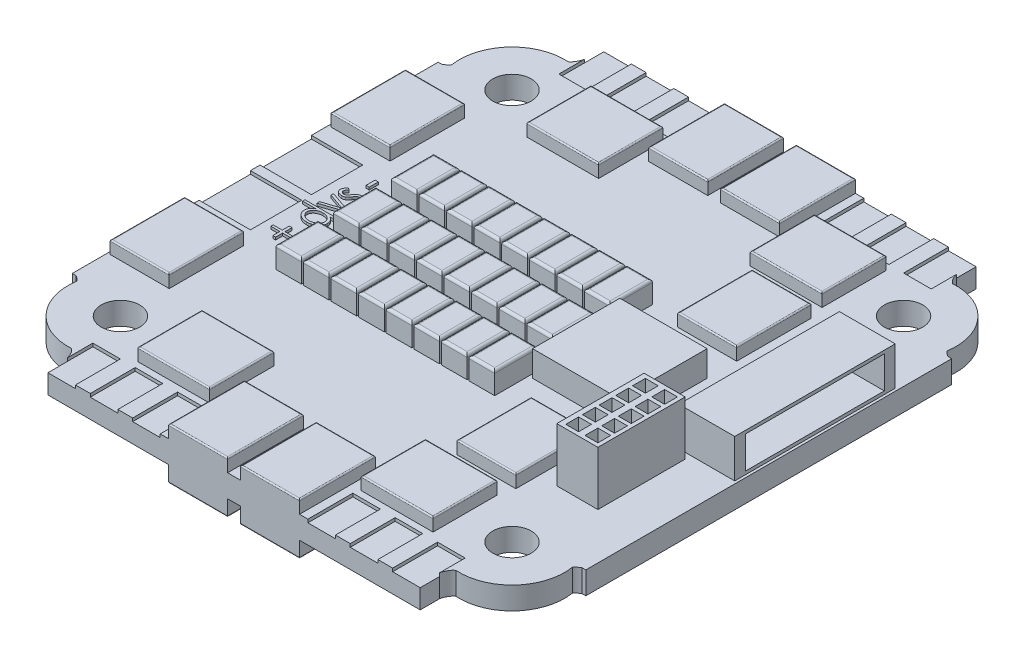
SolidWorks part; units mm, degrees
ref_plane "Ön Düzlem" through (0, 0, 0) normal (0, 0, 1) x (1, 0, 0)
ref_plane "Üst Düzlem" through (0, 0, 0) normal (0, 1, 0) x (1, 0, 0)
ref_plane "Sağ Düzlem" through (0, 0, 0) normal (1, 0, 0) x (0, 0, -1)
sketch "Çizim1" plane through (0, 0, 0) normal (0, 1, 0) x (1, 0, 0)
  line L0 (0, 44.0782) -> (0, -46.2011) construction
  line L1 (20, -21.65) -> (-20, -21.65)
  line L2 (20, -21.65) -> (20, 21.65)
  line L3 (20, 21.65) -> (-20, 21.65)
  line L4 (-20, -21.65) -> (-20, 21.65)
  line L5 (20, -21.65) -> (-20, 21.65) construction
  line L6 (20, 21.65) -> (-20, -21.65) construction
  line L7 (-44.1341, 0) -> (49.6089, 0) construction
  line L9 (15.25, -15.25) -> (-15.25, -15.25) construction
  line L10 (15.25, -15.25) -> (15.25, 15.25) construction
  line L11 (15.25, 15.25) -> (-15.25, 15.25) construction
  line L12 (-15.25, -15.25) -> (-15.25, 15.25) construction
  line L13 (15.25, -15.25) -> (-15.25, 15.25) construction
  line L14 (15.25, 15.25) -> (-15.25, -15.25) construction
  point P0 (0, 0)
  point P10 (0, 0)
  dimension "D1" = 40
  dimension "D2" = 43.3
  dimension "D3" = 30.5
  dimension "D4" = 30.5
extrude "Yükseklik-Ekstrüzyon1" add sketch "Çizim1" along normal blind 1.75
sketch "Çizim2" plane through (0, 0, 0) normal (0, 1, 0) x (1, 0, 0)
  line L1 (15.25, -15.25) -> (-15.25, -15.25) construction
  line L2 (15.25, -15.25) -> (15.25, 15.25) construction
  line L3 (15.25, 15.25) -> (-15.25, 15.25) construction
  line L4 (-15.25, -15.25) -> (-15.25, 15.25) construction
  line L5 (15.25, -15.25) -> (-15.25, 15.25) construction
  line L6 (15.25, 15.25) -> (-15.25, -15.25) construction
  circle A0 centre (-15.25, 15.25) radius 1.5
  circle A1 centre (15.25, 15.25) radius 1.5
  circle A2 centre (15.25, -15.25) radius 1.5
  circle A3 centre (-15.25, -15.25) radius 1.5
  point P0 (0, 0)
  dimension "D1" = 30.5
  dimension "D2" = 30.5
extrude "Kes-Ekstrüzyon1" cut sketch "Çizim2" along normal blind 1.75
sketch "Çizim3" plane through (0, 0, 0) normal (0, 1, 0) x (1, 0, 0)
  line L0 (-19.297, 14.593) -> (-19.4339, 14.3985) construction
  line L1 (-19.4339, 14.3985) -> (-19.7178, 14.25) construction
  line L2 (-20, 21.65) -> (-20, -21.65) construction
  line L3 (-19.7178, 14.25) -> (-20, 14.25)
  line L4 (-20, 21.65) -> (-20, 13.5542) construction
  line L5 (-20, 14.25) -> (-20, 21.65)
  line L6 (-20, 21.65) -> (-14.5, 21.65)
  line L7 (20, 21.65) -> (-20, 21.65) construction
  line L8 (-14.5, 21.65) -> (-14.5, 20.1378)
  line L9 (-14.9713, 19.3405) -> (-14.7537, 19.4813) construction
  line L10 (-14.7537, 19.4813) -> (-14.5714, 19.809) construction
  line L11 (-14.5714, 19.809) -> (-14.5, 20.1378) construction
  line L12 (20, 21.65) -> (14.5, 21.65)
  line L13 (14.5, 21.65) -> (14.5, 20.1378)
  line L14 (14.9713, 19.3405) -> (14.7537, 19.4813) construction
  line L15 (0, 29.2521) -> (0, -30.7082) construction
  line L16 (-36.8808, 0) -> (40.0068, 0) construction
  line L17 (14.7537, 19.4813) -> (14.5714, 19.809) construction
  line L18 (14.5714, 19.809) -> (14.5, 20.1378) construction
  line L19 (20, 14.25) -> (20, 21.65)
  line L20 (19.7178, 14.25) -> (20, 14.25)
  line L21 (19.297, 14.593) -> (19.4339, 14.3985) construction
  line L22 (19.4339, 14.3985) -> (19.7178, 14.25) construction
  line L23 (14.9713, -19.3405) -> (14.7537, -19.4813) construction
  line L24 (14.7537, -19.4813) -> (14.5714, -19.809) construction
  line L25 (14.5714, -19.809) -> (14.5, -20.1378) construction
  line L26 (19.297, -14.593) -> (19.4339, -14.3985) construction
  line L27 (19.4339, -14.3985) -> (19.7178, -14.25) construction
  line L28 (19.7178, -14.25) -> (20, -14.25)
  line L29 (20, -14.25) -> (20, -21.65)
  line L30 (20, -21.65) -> (14.5, -21.65)
  line L31 (14.5, 18.3234) -> (-14.5, 18.3234) construction
  line L32 (14.5, -21.65) -> (14.5, -20.1378)
  line L33 (14.5, 18.3234) -> (14.5, 24.9766) construction
  line L34 (-20, -21.65) -> (-14.5, -21.65)
  line L35 (-14.5, -21.65) -> (-14.5, -20.1378)
  line L36 (-14.9713, -19.3405) -> (-14.7537, -19.4813) construction
  line L37 (-14.7537, -19.4813) -> (-14.5714, -19.809) construction
  line L38 (-14.5714, -19.809) -> (-14.5, -20.1378) construction
  line L39 (-20, -14.25) -> (-20, -21.65)
  line L40 (-19.7178, -14.25) -> (-20, -14.25)
  line L41 (-19.297, -14.593) -> (-19.4339, -14.3985) construction
  line L42 (-19.4339, -14.3985) -> (-19.7178, -14.25) construction
  line L48 (14.5, 24.9766) -> (-14.5, 24.9766) construction
  line L49 (-14.5, 18.3234) -> (-14.5, 24.9766) construction
  line L50 (14.5, 18.3234) -> (-14.5, 24.9766) construction
  line L51 (14.5, 24.9766) -> (-14.5, 18.3234) construction
  line L52 (-14.1712, -14.25) -> (-25.8288, -14.25) construction
  line L53 (-14.1712, -14.25) -> (-14.1712, 14.25) construction
  line L54 (-14.1712, 14.25) -> (-25.8288, 14.25) construction
  line L55 (-25.8288, -14.25) -> (-25.8288, 14.25) construction
  line L56 (-14.1712, -14.25) -> (-25.8288, 14.25) construction
  line L57 (-14.1712, 14.25) -> (-25.8288, -14.25) construction
  arc A0 (14.9713, 19.3405) -> (19.297, 14.593) centre (15.25, 15.25) cw
  circle A1 centre (0, 0) radius 6.746 construction
  arc A2 (14.9713, -19.3405) -> (19.297, -14.593) centre (15.25, -15.25) ccw
  arc A3 (-14.9713, -19.3405) -> (-19.297, -14.593) centre (-15.25, -15.25) cw
  arc A5 (-14.9713, 19.3405) -> (-19.297, 14.593) centre (-15.25, 15.25) ccw
  spline S0 degree 2 poles (-19.297, 14.593) (-19.4339, 14.3985) (-19.7178, 14.25) knots 0 0 0 1 1 1
  spline S1 degree 3 poles (-14.9713, 19.3405) (-14.7537, 19.4813) (-14.5714, 19.809) (-14.5, 20.1378) knots 0 0 0 0 1 1 1 1
  spline S2 degree 3 poles (14.9713, 19.3405) (14.7537, 19.4813) (14.5714, 19.809) (14.5, 20.1378) knots 0 0 0 0 1 1 1 1
  spline S3 degree 2 poles (19.297, 14.593) (19.4339, 14.3985) (19.7178, 14.25) knots 0 0 0 1 1 1
  spline S4 degree 3 poles (14.9713, -19.3405) (14.7537, -19.4813) (14.5714, -19.809) (14.5, -20.1378) knots 0 0 0 0 1 1 1 1
  spline S5 degree 2 poles (19.297, -14.593) (19.4339, -14.3985) (19.7178, -14.25) knots 0 0 0 1 1 1
  spline S6 degree 3 poles (-14.9713, -19.3405) (-14.7537, -19.4813) (-14.5714, -19.809) (-14.5, -20.1378) knots 0 0 0 0 1 1 1 1
  spline S7 degree 2 poles (-19.297, -14.593) (-19.4339, -14.3985) (-19.7178, -14.25) knots 0 0 0 1 1 1
  point P43 (0, 21.65)
  point P61 (-20, 0)
  dimension "D1" = 29
  dimension "D2" = 28.5
extrude "Kes-Ekstrüzyon4" cut sketch "Çizim3" along normal blind 1.75
sketch "Çizim5" plane through (0, 0, 0) normal (0, 1, 0) x (1, 0, 0)
  line L0 (0, 30.9186) -> (0, -32.6939) construction
  line L1 (-49.0396, 0) -> (40.1136, 0) construction
  line L2 (-10.125, 21.65) -> (-10.125, 17.2464) construction
  line L3 (-14.5, 21.65) -> (-5.75, 21.65) construction
  line L4 (-14.5, 21.65) -> (-14.5, 18.15) construction
  line L5 (-14.5, 18.15) -> (-5.75, 18.15) construction
  line L6 (-5.75, 21.65) -> (-5.75, 18.15) construction
  line L7 (-14.5, 21.65) -> (-12.3523, 21.65)
  line L8 (-14.5, 21.65) -> (-14.5, 18.15)
  line L9 (-14.5, 18.15) -> (-12.3523, 18.15)
  line L10 (-12.3523, 21.65) -> (-12.3523, 18.15)
  line L11 (-5.75, 18.15) -> (-7.8977, 18.15)
  line L12 (-5.75, 21.65) -> (-5.75, 18.15)
  line L13 (-5.75, 21.65) -> (-7.8977, 21.65)
  line L14 (-7.8977, 21.65) -> (-7.8977, 18.15)
  line L15 (-5.75, 19.9) -> (-14.5, 19.9) construction
  line L16 (9.05, 21.65) -> (11.2, 18.15) construction
  line L17 (-9.05, 18.15) -> (-11.2, 18.15)
  line L18 (-9.05, 18.15) -> (-9.05, 21.65)
  line L19 (-9.05, 21.65) -> (-11.2, 21.65)
  line L20 (-11.2, 18.15) -> (-11.2, 21.65)
  line L21 (-9.05, 18.15) -> (-11.2, 21.65) construction
  line L22 (-9.05, 21.65) -> (-11.2, 18.15) construction
  line L23 (9.05, 18.15) -> (11.2, 21.65) construction
  line L24 (5.75, 19.9) -> (14.5, 19.9) construction
  line L25 (5.75, 21.65) -> (5.75, 18.15) construction
  line L26 (14.5, 18.15) -> (5.75, 18.15) construction
  line L27 (14.5, 21.65) -> (14.5, 18.15) construction
  line L28 (14.5, 21.65) -> (5.75, 21.65) construction
  line L29 (10.125, 21.65) -> (10.125, 17.2464) construction
  line L30 (11.2, 18.15) -> (11.2, 21.65)
  line L31 (9.05, 21.65) -> (11.2, 21.65)
  line L32 (9.05, 18.15) -> (9.05, 21.65)
  line L33 (9.05, 18.15) -> (11.2, 18.15)
  line L34 (7.8977, 21.65) -> (7.8977, 18.15)
  line L35 (5.75, 21.65) -> (7.8977, 21.65)
  line L36 (5.75, 21.65) -> (5.75, 18.15)
  line L37 (5.75, 18.15) -> (7.8977, 18.15)
  line L38 (12.3523, 21.65) -> (12.3523, 18.15)
  line L39 (14.5, 18.15) -> (12.3523, 18.15)
  line L40 (14.5, 21.65) -> (14.5, 18.15)
  line L41 (14.5, 21.65) -> (12.3523, 21.65)
  line L42 (10.125, -21.65) -> (10.125, -17.2464) construction
  line L43 (14.5, -21.65) -> (5.75, -21.65) construction
  line L44 (14.5, -21.65) -> (14.5, -18.15) construction
  line L45 (14.5, -18.15) -> (5.75, -18.15) construction
  line L46 (5.75, -21.65) -> (5.75, -18.15) construction
  line L47 (5.75, -19.9) -> (14.5, -19.9) construction
  line L48 (9.05, -18.15) -> (11.2, -21.65) construction
  line L49 (-9.05, -21.65) -> (-11.2, -18.15) construction
  line L50 (-9.05, -18.15) -> (-11.2, -21.65) construction
  line L51 (9.05, -21.65) -> (11.2, -18.15) construction
  line L52 (-5.75, -19.9) -> (-14.5, -19.9) construction
  line L53 (-5.75, -21.65) -> (-5.75, -18.15) construction
  line L54 (-14.5, -18.15) -> (-5.75, -18.15) construction
  line L55 (-14.5, -21.65) -> (-14.5, -18.15) construction
  line L56 (-14.5, -21.65) -> (-5.75, -21.65) construction
  line L57 (-10.125, -21.65) -> (-10.125, -17.2464) construction
  line L58 (14.5, -21.65) -> (12.3523, -21.65)
  line L59 (14.5, -21.65) -> (14.5, -18.15)
  line L60 (14.5, -18.15) -> (12.3523, -18.15)
  line L61 (12.3523, -21.65) -> (12.3523, -18.15)
  line L62 (5.75, -18.15) -> (7.8977, -18.15)
  line L63 (5.75, -21.65) -> (5.75, -18.15)
  line L64 (5.75, -21.65) -> (7.8977, -21.65)
  line L65 (7.8977, -21.65) -> (7.8977, -18.15)
  line L66 (9.05, -18.15) -> (11.2, -18.15)
  line L67 (9.05, -18.15) -> (9.05, -21.65)
  line L68 (9.05, -21.65) -> (11.2, -21.65)
  line L69 (11.2, -18.15) -> (11.2, -21.65)
  line L70 (-11.2, -18.15) -> (-11.2, -21.65)
  line L71 (-9.05, -21.65) -> (-11.2, -21.65)
  line L72 (-9.05, -18.15) -> (-9.05, -21.65)
  line L73 (-9.05, -18.15) -> (-11.2, -18.15)
  line L74 (-7.8977, -21.65) -> (-7.8977, -18.15)
  line L75 (-5.75, -21.65) -> (-7.8977, -21.65)
  line L76 (-5.75, -21.65) -> (-5.75, -18.15)
  line L77 (-5.75, -18.15) -> (-7.8977, -18.15)
  line L78 (-12.3523, -21.65) -> (-12.3523, -18.15)
  line L79 (-14.5, -18.15) -> (-12.3523, -18.15)
  line L80 (-14.5, -21.65) -> (-14.5, -18.15)
  line L81 (-14.5, -21.65) -> (-12.3523, -21.65)
  point P18 (-10.125, 19.9)
  point P39 (10.125, 19.9)
  point P72 (10.125, -19.9)
  point P73 (-10.125, -19.9)
  dimension "D1" = 8.75
  dimension "D2" = 3.5
  dimension "D3" = 2.15
extrude "Kes-Ekstrüzyon5" cut sketch "Çizim5" along normal blind 1 from offset 1.5
sketch "Çizim6" plane through (0, 0, 0) normal (0, 1, 0) x (1, 0, 0)
  line L0 (-37.3382, 0) -> (45.0839, 0) construction
  line L1 (-20, 14.25) -> (-20, -14.25) construction
  line L2 (-15.9, -4.375) -> (-20, -4.375) construction
  line L3 (-15.9, -4.375) -> (-15.9, 4.375) construction
  line L4 (-15.9, 4.375) -> (-20, 4.375) construction
  line L5 (-20, -4.375) -> (-20, 4.375) construction
  line L6 (-15.9, -4.375) -> (-20, 4.375) construction
  line L7 (-15.9, 4.375) -> (-20, -4.375) construction
  line L8 (-20, -4.375) -> (-20, -0.375)
  line L9 (-20, 4.375) -> (-16, 4.375)
  line L10 (-20, 4.375) -> (-20, 0.375)
  line L11 (-20, 0.375) -> (-16, 0.375)
  line L12 (-16, 4.375) -> (-16, 0.375)
  line L13 (-20, -4.375) -> (-16, -4.375)
  line L14 (-16, -4.375) -> (-16, -0.375)
  line L15 (-20, -0.375) -> (-16, -0.375)
  point P3 (-17.95, 0)
  dimension "D1" = 8.75
  dimension "D2" = 4.1
  dimension "D3" = 4
  dimension "D4" = 4
extrude "Kes-Ekstrüzyon7" cut sketch "Çizim6" along normal blind 1 from offset 1.5
sketch "Çizim7" plane through (0, 0, 0) normal (0, 1, 0) x (1, 0, 0)
  line L0 (12, 0) -> (-20, 0) construction
  line L1 (-20, 14.25) -> (-20, 4.375) construction
  line L2 (-15.2, -11.5) -> (-20, -11.5) construction
  line L3 (-15.2, -11.5) -> (-15.2, 11.5) construction
  line L4 (-15.2, 11.5) -> (-20, 11.5) construction
  line L5 (-20, -11.5) -> (-20, 11.5) construction
  line L6 (-15.2, -11.5) -> (-20, 11.5) construction
  line L7 (-15.2, 11.5) -> (-20, -11.5) construction
  line L8 (-19.8, 11.9264) -> (-19.8, -13.8708) construction
  line L9 (-19.8, -11.5) -> (-15.2, -11.5)
  line L10 (-19.8, 11.5) -> (-15.2, 11.5)
  line L11 (-19.8, 11.5) -> (-19.8, 5.7)
  line L12 (-19.8, 5.7) -> (-15.2, 5.7)
  line L13 (-15.2, 11.5) -> (-15.2, 5.7)
  line L14 (-15.2, -11.5) -> (-15.2, -5.7)
  line L15 (-19.8, -11.5) -> (-19.8, -5.7)
  line L16 (-19.8, -5.7) -> (-15.2, -5.7)
  line L17 (12, 23.8694) -> (12, -27.9826) construction
  line L18 (20, -14.25) -> (20, 14.25) construction
  line L19 (-20, 21.0492) -> (-20, -26.7007) construction
  line L20 (-4, 16.02) -> (-4, -18.6893) construction
  line L21 (11.8, -11.5) -> (11.8, -5.7)
  line L22 (11.8, -11.5) -> (7.2, -11.5)
  line L23 (7.2, -11.5) -> (7.2, -5.7)
  line L24 (11.8, -5.7) -> (7.2, -5.7)
  line L25 (11.8, 11.5) -> (11.8, 5.7)
  line L26 (11.8, 5.7) -> (7.2, 5.7)
  line L27 (7.2, 11.5) -> (7.2, 5.7)
  line L28 (11.8, 11.5) -> (7.2, 11.5)
  point P3 (-17.6, 0)
  point P16 (-17.5, -11.5)
  point P19 (-17.5, -5.7)
  dimension "D1" = 23
  dimension "D2" = 0.2
  dimension "D3" = 5.8
  dimension "D4" = 8
extrude "Yükseklik-Ekstrüzyon2" add sketch "Çizim7" along normal blind 2.75 and the other way blind 1.25
sketch "Çizim9" plane through (0, 0, 0) normal (0, 1, 0) x (1, 0, 0)
  line L0 (11.8, 15.4181) -> (11.8, -15.0147) construction
  line L1 (-13.0732, 0) -> (28.7719, 0) construction
  line L2 (-13.0732, 3.4) -> (30.1552, 3.4) construction
  line L4 (11.8, 3.4) -> (5, 3.4)
  line L5 (11.8, 3.4) -> (11.8, -3.4)
  line L6 (11.8, -3.4) -> (5, -3.4)
  line L7 (5, 3.4) -> (5, -3.4)
  dimension "D1" = 3.4
  dimension "D2" = 6.8
  dimension "D3" = 6.8
extrude "Yükseklik-Ekstrüzyon3" add sketch "Çizim9" along normal blind 3.75
sketch "Çizim10" plane through (0, 0, 0) normal (0, 1, 0) x (1, 0, 0)
  line L0 (0, 23.2569) -> (0, -24.4096) construction
  line L1 (5.75, 21.65) -> (-5.75, 21.65) construction
  line L2 (5.1, 15.75) -> (-5.1, 15.75) construction
  line L3 (5.1, 15.75) -> (5.1, 21.65) construction
  line L4 (5.1, 21.65) -> (-5.1, 21.65) construction
  line L5 (-5.1, 15.75) -> (-5.1, 21.65) construction
  line L6 (5.1, 15.75) -> (-5.1, 21.65) construction
  line L7 (5.1, 21.65) -> (-5.1, 15.75) construction
  line L8 (-5.1, 15.75) -> (-0.5021, 15.75)
  line L9 (5.1, 21.65) -> (0.5021, 21.65)
  line L10 (5.1, 21.65) -> (5.1, 15.75)
  line L11 (5.1, 15.75) -> (0.5021, 15.75)
  line L12 (0.5021, 21.65) -> (0.5021, 15.75)
  line L13 (-0.5021, 21.65) -> (-0.5021, 15.75)
  line L14 (-5.1, 21.65) -> (-0.5021, 21.65)
  line L15 (-5.1, 21.65) -> (-5.1, 15.75)
  line L16 (-34.7799, 0) -> (34.025, 0) construction
  line L17 (-17.6922, 17.65) -> (20.1896, 17.65) construction
  line L18 (-12.3523, 18.15) -> (-14.5, 18.15) construction
  line L19 (-17.6922, 15.15) -> (18.3088, 15.15) construction
  line L20 (11.5, 17.65) -> (11.5, 12.65)
  line L21 (11.5, 12.65) -> (-11.5, 12.65) construction
  line L22 (11.5, 12.65) -> (11.5, 17.65) construction
  line L23 (11.5, 17.65) -> (-11.5, 17.65) construction
  line L24 (-11.5, 12.65) -> (-11.5, 17.65) construction
  line L25 (11.5, 12.65) -> (-11.5, 17.65) construction
  line L26 (11.5, 17.65) -> (-11.5, 12.65) construction
  line L27 (-11.5, 17.65) -> (-5.9038, 17.65)
  line L28 (-11.5, 17.65) -> (-11.5, 12.65)
  line L29 (-11.5, 12.65) -> (-5.9038, 12.65)
  line L30 (-5.9038, 17.65) -> (-5.9038, 12.65)
  line L31 (11.5, 17.65) -> (5.9038, 17.65)
  line L32 (5.9038, 17.65) -> (5.9038, 12.65)
  line L33 (11.5, 12.65) -> (5.9038, 12.65)
  line L34 (11.5, -17.65) -> (-11.5, -12.65) construction
  line L35 (11.5, -12.65) -> (-11.5, -17.65) construction
  line L36 (-11.5, -12.65) -> (-11.5, -17.65) construction
  line L37 (11.5, -17.65) -> (-11.5, -17.65) construction
  line L38 (11.5, -12.65) -> (11.5, -17.65) construction
  line L39 (11.5, -12.65) -> (-11.5, -12.65) construction
  line L40 (-17.6922, -15.15) -> (18.3088, -15.15) construction
  line L41 (-17.6922, -17.65) -> (20.1896, -17.65) construction
  line L42 (5.1, -21.65) -> (-5.1, -15.75) construction
  line L43 (5.1, -15.75) -> (-5.1, -21.65) construction
  line L44 (-5.1, -15.75) -> (-5.1, -21.65) construction
  line L45 (5.1, -21.65) -> (-5.1, -21.65) construction
  line L46 (5.1, -15.75) -> (5.1, -21.65) construction
  line L47 (5.1, -15.75) -> (-5.1, -15.75) construction
  line L48 (0, -23.2569) -> (0, 24.4096) construction
  line L49 (11.5, -12.65) -> (5.9038, -12.65)
  line L50 (5.9038, -17.65) -> (5.9038, -12.65)
  line L51 (11.5, -17.65) -> (5.9038, -17.65)
  line L52 (-5.9038, -17.65) -> (-5.9038, -12.65)
  line L53 (-11.5, -12.65) -> (-5.9038, -12.65)
  line L54 (-11.5, -17.65) -> (-11.5, -12.65)
  line L55 (-11.5, -17.65) -> (-5.9038, -17.65)
  line L56 (11.5, -17.65) -> (11.5, -12.65)
  line L57 (-5.1, -21.65) -> (-5.1, -15.75)
  line L58 (-5.1, -21.65) -> (-0.5021, -21.65)
  line L59 (-0.5021, -21.65) -> (-0.5021, -15.75)
  line L60 (0.5021, -21.65) -> (0.5021, -15.75)
  line L61 (5.1, -15.75) -> (0.5021, -15.75)
  line L62 (5.1, -21.65) -> (5.1, -15.75)
  line L63 (5.1, -21.65) -> (0.5021, -21.65)
  line L64 (-5.1, -15.75) -> (-0.5021, -15.75)
  line L65 (-5.7307, 22.4988) -> (4.1432, 22.4988) construction
  point P3 (0, 18.7)
  point P22 (0, 15.15)
  point P53 (0, -15.15)
  point P54 (0, -18.7)
  dimension "D1" = 10.2
  dimension "D2" = 5.9
  dimension "D3" = 0.5
  dimension "D4" = 2.5
  dimension "D5" = 23
  dimension "D6" = 5.5962
  dimension "D7" = 0.8488
extrude "Yükseklik-Ekstrüzyon4" add sketch "Çizim10" along normal blind 2.75 and the other way blind 1.25
sketch "Çizim11" plane through (0, 0, 0) normal (0, 1, 0) x (1, 0, 0)
  line L0 (-37.3419, -0.2797) -> (45.0802, -0.2797) construction
  line L1 (-15.9037, -4.6547) -> (-20.0037, -4.6547) construction
  line L2 (-15.9037, -4.6547) -> (-15.9037, 4.0953) construction
  line L3 (-15.9037, 4.0953) -> (-20.0037, 4.0953) construction
  line L4 (-20.0037, -4.6547) -> (-20.0037, 4.0953) construction
  line L5 (-15.9037, -4.6547) -> (-20.0037, 4.0953) construction
  line L6 (-15.9037, 4.0953) -> (-20.0037, -4.6547) construction
  line L7 (-20.0037, -4.6547) -> (-20.0037, -0.6547)
  line L8 (-20.0037, 4.0953) -> (-16.0037, 4.0953)
  line L9 (-20.0037, 4.0953) -> (-20.0037, 0.0953)
  line L10 (-20.0037, 0.0953) -> (-16.0037, 0.0953)
  line L11 (-16.0037, 4.0953) -> (-16.0037, 0.0953)
  line L12 (-20.0037, -4.6547) -> (-16.0037, -4.6547)
  line L13 (-16.0037, -4.6547) -> (-16.0037, -0.6547)
  line L14 (-20.0037, -0.6547) -> (-16.0037, -0.6547)
  point P2 (-17.9537, -0.2797)
  dimension "D1" = 8.75
  dimension "D2" = 4.1
  dimension "D3" = 4
  dimension "D4" = 4
extrude "Kes-Ekstrüzyon8" cut sketch "Çizim11" along normal blind 0.5
sketch "Çizim12" plane through (0, 0, 0) normal (0, 1, 0) x (1, 0, 0)
  line L0 (20, 14.25) -> (29.4504, 14.25) construction
  line L1 (32.1594, 10.05) -> (-8.1295, 10.05) construction
  line L2 (19.8, 11.0054) -> (19.8, -21.7671) construction
  line L3 (20, -14.25) -> (20, 14.25) construction
  line L5 (19.8, 10.05) -> (15.45, 10.05)
  line L6 (19.8, 10.05) -> (19.8, -2.45)
  line L7 (19.8, -2.45) -> (15.45, -2.45)
  line L8 (15.45, 10.05) -> (15.45, -2.45)
  dimension "D1" = 4.2
  dimension "D2" = 0.2
  dimension "D3" = 12.5
  dimension "D4" = 4.35
extrude "Yükseklik-Ekstrüzyon5" add sketch "Çizim12" along normal blind 3 from surface starting at face at (-1.6364, 1.75, 0)
ref_plane "Düzlem1" through (29.8, 0, 0) normal (1, 0, 0) x (0, 0, -1)
sketch "Çizim13" plane through (29.8, 0, 0) normal (1, 0, 0) x (0, 0, -1)
  line L0 (3.8, 4.75) -> (3.8, 1.086) construction
  line L1 (10.05, 4.75) -> (-2.45, 4.75) construction
  line L2 (-2.45, 3.25) -> (10.05, 3.25) construction
  line L3 (-2.45, 4.75) -> (-2.45, 1.75) construction
  line L4 (10.05, 4.75) -> (10.05, 1.75) construction
  line L6 (9.2, 2) -> (-1.6, 2)
  line L7 (9.2, 2) -> (9.2, 4.5)
  line L8 (9.2, 4.5) -> (-1.6, 4.5)
  line L9 (-1.6, 2) -> (-1.6, 4.5)
  line L10 (9.2, 2) -> (-1.6, 4.5) construction
  line L11 (9.2, 4.5) -> (-1.6, 2) construction
  point P10 (3.8, 3.25)
  dimension "D1" = 10.8
  dimension "D2" = 2.5
extrude "Kes-Ekstrüzyon9" cut sketch "Çizim13" against normal blind 13
sketch "Çizim14" plane through (0, 0, 0) normal (0, 1, 0) x (1, 0, 0)
  line L0 (16.4, 0.4899) -> (16.4, -23.3722) construction
  line L1 (20, -14.25) -> (20, 14.25) construction
  line L2 (20, -2.9107) -> (10.3037, -2.9107) construction
  line L4 (16.4, -2.9107) -> (13.2, -2.9107)
  line L5 (16.4, -2.9107) -> (16.4, -9.7107)
  line L6 (16.4, -9.7107) -> (13.2, -9.7107)
  line L7 (13.2, -2.9107) -> (13.2, -9.7107)
  dimension "D1" = 3.6
  dimension "D2" = 3.2
  dimension "D3" = 6.8
extrude "Yükseklik-Ekstrüzyon6" add sketch "Çizim14" along normal blind 4.2 from surface starting at face at (17.625, 1.75, -3.8)
ref_plane "Düzlem2" through (0, 5.95, 0) normal (0, 1, 0) x (1, 0, 0)
sketch "Çizim15" plane through (0, 5.95, 0) normal (0, 1, 0) x (1, 0, 0)
  line L0 (14.8, -2.9107) -> (14.8, -11.4983) construction
  line L1 (13.2, -2.9107) -> (16.4, -2.9107) construction
  line L2 (13.2, -6.3107) -> (18.1949, -6.3107) construction
  line L3 (13.2, -9.7107) -> (13.2, -2.9107) construction
  line L4 (17.215, -3.2107) -> (12.1271, -3.2107) construction
  line L5 (13.2, -2.9107) -> (16.4, -2.9107) construction
  line L6 (14.8, -2.9107) -> (16.4, -2.9107) construction
  line L7 (15.6, -2.9107) -> (15.6, -10.0902) construction
  line L8 (15.1, -2.7946) -> (15.1, -11.569) construction
  line L9 (16.1, -2.7946) -> (16.1, -11.569) construction
  line L10 (13.6, -4.213) -> (14.6, -4.213)
  line L11 (15.1, -3.2107) -> (16.1, -3.2107)
  line L12 (15.1, -3.2107) -> (15.1, -4.213)
  line L13 (15.1, -4.213) -> (16.1, -4.213)
  line L14 (16.1, -3.2107) -> (16.1, -4.213)
  line L15 (14.6, -3.2107) -> (14.6, -4.213)
  line L16 (13.6, -3.2107) -> (14.6, -3.2107)
  line L17 (13.6, -3.2107) -> (13.6, -4.213)
  line L18 (13.6, -5.513) -> (14.6, -5.513)
  line L19 (14.6, -4.5107) -> (14.6, -5.513)
  line L20 (13.6, -4.5107) -> (14.6, -4.5107)
  line L21 (13.6, -4.5107) -> (13.6, -5.513)
  line L22 (13.6, -6.813) -> (14.6, -6.813)
  line L23 (14.6, -5.8107) -> (14.6, -6.813)
  line L24 (13.6, -5.8107) -> (14.6, -5.8107)
  line L25 (13.6, -5.8107) -> (13.6, -6.813)
  line L26 (13.6, -8.113) -> (14.6, -8.113)
  line L27 (14.6, -7.1107) -> (14.6, -8.113)
  line L28 (13.6, -7.1107) -> (14.6, -7.1107)
  line L29 (13.6, -7.1107) -> (13.6, -8.113)
  line L30 (13.6, -9.413) -> (14.6, -9.413)
  line L31 (14.6, -8.4107) -> (14.6, -9.413)
  line L32 (13.6, -8.4107) -> (14.6, -8.4107)
  line L33 (13.6, -8.4107) -> (13.6, -9.413)
  line L34 (15.1, -5.513) -> (16.1, -5.513)
  line L35 (16.1, -4.5107) -> (16.1, -5.513)
  line L36 (15.1, -4.5107) -> (16.1, -4.5107)
  line L37 (15.1, -4.5107) -> (15.1, -5.513)
  line L38 (15.1, -6.813) -> (16.1, -6.813)
  line L39 (16.1, -5.8107) -> (16.1, -6.813)
  line L40 (15.1, -5.8107) -> (16.1, -5.8107)
  line L41 (15.1, -5.8107) -> (15.1, -6.813)
  line L42 (15.1, -8.113) -> (16.1, -8.113)
  line L43 (16.1, -7.1107) -> (16.1, -8.113)
  line L44 (15.1, -7.1107) -> (16.1, -7.1107)
  line L45 (15.1, -7.1107) -> (15.1, -8.113)
  line L46 (15.1, -9.413) -> (16.1, -9.413)
  line L47 (16.1, -8.4107) -> (16.1, -9.413)
  line L48 (15.1, -8.4107) -> (16.1, -8.4107)
  line L49 (15.1, -8.4107) -> (15.1, -9.413)
  point P18 (15.6, -3.6747)
  dimension "D1" = 0.3
  dimension "D2" = 2
  dimension "D3" = 5
extrude "Kes-Ekstrüzyon10" cut sketch "Çizim15" against normal blind 3
sketch "Çizim16" plane through (0, 0, 0) normal (0, 1, 0) x (1, 0, 0)
  line L0 (-12.5, 22.9111) -> (-12.5, -24.352) construction
  line L1 (-20, 0.375) -> (-20, -0.375) construction
  line L2 (-30.7148, 0) -> (26.2314, 0) construction
  line L3 (-26.6801, 6.25) -> (27.3842, 6.25) construction
  line L4 (-4.2014, 6.25) -> (-4.2014, 0) construction
  line L5 (-12.5, 6.25) -> (4.7, 6.25) construction
  line L6 (-12.5, 6.25) -> (-12.5, -6.25) construction
  line L7 (-12.5, -6.25) -> (4.7, -6.25) construction
  line L8 (4.7, 6.25) -> (4.7, -6.25) construction
  line L9 (-13.8057, 2.95) -> (8.3849, 2.95) construction
  line L10 (0.55, 6.25) -> (0.55, 2.95)
  line L11 (4.7, 6.25) -> (2.7, 6.25)
  line L12 (4.7, 6.25) -> (4.7, 2.95)
  line L13 (4.7, 2.95) -> (2.7, 2.95)
  line L14 (2.7, 6.25) -> (2.7, 2.95)
  line L15 (2.55, 6.25) -> (0.55, 6.25)
  line L16 (2.55, 6.25) -> (2.55, 2.95)
  line L17 (2.55, 2.95) -> (0.55, 2.95)
  line L18 (-1.6, 6.25) -> (-1.6, 2.95)
  line L19 (0.4, 6.25) -> (-1.6, 6.25)
  line L20 (0.4, 6.25) -> (0.4, 2.95)
  line L21 (0.4, 2.95) -> (-1.6, 2.95)
  line L22 (-3.75, 6.25) -> (-3.75, 2.95)
  line L23 (-1.75, 6.25) -> (-3.75, 6.25)
  line L24 (-1.75, 6.25) -> (-1.75, 2.95)
  line L25 (-1.75, 2.95) -> (-3.75, 2.95)
  line L26 (-5.9, 6.25) -> (-5.9, 2.95)
  line L27 (-3.9, 6.25) -> (-5.9, 6.25)
  line L28 (-3.9, 6.25) -> (-3.9, 2.95)
  line L29 (-3.9, 2.95) -> (-5.9, 2.95)
  line L30 (-8.05, 6.25) -> (-8.05, 2.95)
  line L31 (-6.05, 6.25) -> (-8.05, 6.25)
  line L32 (-6.05, 6.25) -> (-6.05, 2.95)
  line L33 (-6.05, 2.95) -> (-8.05, 2.95)
  line L34 (-10.2, 6.25) -> (-10.2, 2.95)
  line L35 (-8.2, 6.25) -> (-10.2, 6.25)
  line L36 (-8.2, 6.25) -> (-8.2, 2.95)
  line L37 (-8.2, 2.95) -> (-10.2, 2.95)
  line L38 (-12.35, 6.25) -> (-12.35, 2.95)
  line L39 (-10.35, 6.25) -> (-12.35, 6.25)
  line L40 (-10.35, 6.25) -> (-10.35, 2.95)
  line L41 (-10.35, 2.95) -> (-12.35, 2.95)
  line L42 (0.55, 1.75) -> (0.55, -1.55)
  line L43 (2.55, 1.75) -> (0.55, 1.75)
  line L44 (2.55, 1.75) -> (2.55, -1.55)
  line L45 (2.55, -1.55) -> (0.55, -1.55)
  line L46 (-1.6, 1.75) -> (-1.6, -1.55)
  line L47 (0.4, 1.75) -> (-1.6, 1.75)
  line L48 (0.4, 1.75) -> (0.4, -1.55)
  line L49 (0.4, -1.55) -> (-1.6, -1.55)
  line L50 (-3.75, 1.75) -> (-3.75, -1.55)
  line L51 (-1.75, 1.75) -> (-3.75, 1.75)
  line L52 (-1.75, 1.75) -> (-1.75, -1.55)
  line L53 (-1.75, -1.55) -> (-3.75, -1.55)
  line L54 (-5.9, 1.75) -> (-5.9, -1.55)
  line L55 (-3.9, 1.75) -> (-5.9, 1.75)
  line L56 (-3.9, 1.75) -> (-3.9, -1.55)
  line L57 (-3.9, -1.55) -> (-5.9, -1.55)
  line L58 (-8.05, 1.75) -> (-8.05, -1.55)
  line L59 (-6.05, 1.75) -> (-8.05, 1.75)
  line L60 (-6.05, 1.75) -> (-6.05, -1.55)
  line L61 (-6.05, -1.55) -> (-8.05, -1.55)
  line L62 (-10.2, 1.75) -> (-10.2, -1.55)
  line L63 (-8.2, 1.75) -> (-10.2, 1.75)
  line L64 (-8.2, 1.75) -> (-8.2, -1.55)
  line L65 (-8.2, -1.55) -> (-10.2, -1.55)
  line L66 (-12.35, 1.75) -> (-12.35, -1.55)
  line L67 (-10.35, 1.75) -> (-12.35, 1.75)
  line L68 (-10.35, 1.75) -> (-10.35, -1.55)
  line L69 (-10.35, -1.55) -> (-12.35, -1.55)
  line L70 (0.55, -2.75) -> (0.55, -6.05)
  line L71 (2.55, -2.75) -> (0.55, -2.75)
  line L72 (2.55, -2.75) -> (2.55, -6.05)
  line L73 (2.55, -6.05) -> (0.55, -6.05)
  line L74 (-1.6, -2.75) -> (-1.6, -6.05)
  line L75 (0.4, -2.75) -> (-1.6, -2.75)
  line L76 (0.4, -2.75) -> (0.4, -6.05)
  line L77 (0.4, -6.05) -> (-1.6, -6.05)
  line L78 (-3.75, -2.75) -> (-3.75, -6.05)
  line L79 (-1.75, -2.75) -> (-3.75, -2.75)
  line L80 (-1.75, -2.75) -> (-1.75, -6.05)
  line L81 (-1.75, -6.05) -> (-3.75, -6.05)
  line L82 (-5.9, -2.75) -> (-5.9, -6.05)
  line L83 (-3.9, -2.75) -> (-5.9, -2.75)
  line L84 (-3.9, -2.75) -> (-3.9, -6.05)
  line L85 (-3.9, -6.05) -> (-5.9, -6.05)
  line L86 (-8.05, -2.75) -> (-8.05, -6.05)
  line L87 (-6.05, -2.75) -> (-8.05, -2.75)
  line L88 (-6.05, -2.75) -> (-6.05, -6.05)
  line L89 (-6.05, -6.05) -> (-8.05, -6.05)
  line L90 (-10.2, -2.75) -> (-10.2, -6.05)
  line L91 (-8.2, -2.75) -> (-10.2, -2.75)
  line L92 (-8.2, -2.75) -> (-8.2, -6.05)
  line L93 (-8.2, -6.05) -> (-10.2, -6.05)
  line L94 (-12.35, -2.75) -> (-12.35, -6.05)
  line L95 (-10.35, -2.75) -> (-12.35, -2.75)
  line L96 (-10.35, -2.75) -> (-10.35, -6.05)
  line L97 (-10.35, -6.05) -> (-12.35, -6.05)
  line L98 (2.7, 1.75) -> (2.7, -1.55)
  line L99 (4.7, 1.75) -> (2.7, 1.75)
  line L100 (4.7, 1.75) -> (4.7, -1.55)
  line L101 (4.7, -1.55) -> (2.7, -1.55)
  line L102 (2.7, -2.75) -> (2.7, -6.05)
  line L103 (4.7, -2.75) -> (2.7, -2.75)
  line L104 (4.7, -2.75) -> (4.7, -6.05)
  line L105 (4.7, -6.05) -> (2.7, -6.05)
  dimension "D1" = 7.5
  dimension "D2" = 6.25
  dimension "D3" = 17.2
  dimension "D4" = 12.5
  dimension "D5" = 2
  dimension "D6" = 3.3
  dimension "D7" = 8
  dimension "D8" = 3
extrude "Yükseklik-Ekstrüzyon7" add sketch "Çizim16" along normal blind 3.45
fillet "Radyus1" radius 0.2 96 edges at (-11.35, 3.45, 6.05) (-12.35, 3.45, 4.4) (-11.35, 3.45, 2.75) (-10.35, 3.45, 4.4) (-9.2, 3.45, 6.05) (-10.2, 3.45, 4.4) (-9.2, 3.45, 2.75) (-8.2, 3.45, 4.4) (-7.05, 3.45, 6.05) (-8.05, 3.45, 4.4) (-7.05, 3.45, 2.75) (-6.05, 3.45, 4.4) (-4.9, 3.45, 6.05) (-5.9, 3.45, 4.4) (-4.9, 3.45, 2.75) (-3.9, 3.45, 4.4) (-2.75, 3.45, 6.05) (-3.75, 3.45, 4.4) (-2.75, 3.45, 2.75) (-1.75, 3.45, 4.4) (-0.6, 3.45, 6.05) (-1.6, 3.45, 4.4) (-0.6, 3.45, 2.75) (0.4, 3.45, 4.4) (1.55, 3.45, 6.05) (0.55, 3.45, 4.4) (1.55, 3.45, 2.75) (2.55, 3.45, 4.4) (3.7, 3.45, 6.05) (2.7, 3.45, 4.4) (3.7, 3.45, 2.75) (4.7, 3.45, 4.4) (3.7, 3.45, 1.55) (2.7, 3.45, -0.1) (3.7, 3.45, -1.75) (4.7, 3.45, -0.1) (1.55, 3.45, 1.55) (0.55, 3.45, -0.1) (1.55, 3.45, -1.75) (2.55, 3.45, -0.1) (-0.6, 3.45, 1.55) (-1.6, 3.45, -0.1) (-0.6, 3.45, -1.75) (0.4, 3.45, -0.1) (-2.75, 3.45, 1.55) (-3.75, 3.45, -0.1) (-2.75, 3.45, -1.75) (-1.75, 3.45, -0.1) (-4.9, 3.45, 1.55) (-5.9, 3.45, -0.1) (-4.9, 3.45, -1.75) (-3.9, 3.45, -0.1) (-7.05, 3.45, 1.55) (-8.05, 3.45, -0.1) (-7.05, 3.45, -1.75) (-6.05, 3.45, -0.1) (-9.2, 3.45, 1.55) (-10.2, 3.45, -0.1) (-9.2, 3.45, -1.75) (-8.2, 3.45, -0.1) (-11.35, 3.45, 1.55) (-12.35, 3.45, -0.1) (-11.35, 3.45, -1.75) (-10.35, 3.45, -0.1) (3.7, 3.45, -2.95) (2.7, 3.45, -4.6) (3.7, 3.45, -6.25) (4.7, 3.45, -4.6) (1.55, 3.45, -2.95) (0.55, 3.45, -4.6) (1.55, 3.45, -6.25) (2.55, 3.45, -4.6) (-0.6, 3.45, -2.95) (-1.6, 3.45, -4.6) (-0.6, 3.45, -6.25) (0.4, 3.45, -4.6) (-2.75, 3.45, -2.95) (-3.75, 3.45, -4.6) (-2.75, 3.45, -6.25) (-1.75, 3.45, -4.6) (-4.9, 3.45, -2.95) (-5.9, 3.45, -4.6) (-4.9, 3.45, -6.25) (-3.9, 3.45, -4.6) (-7.05, 3.45, -2.95) (-8.05, 3.45, -4.6) (-7.05, 3.45, -6.25) (-6.05, 3.45, -4.6) (-9.2, 3.45, -2.95) (-10.2, 3.45, -4.6) (-9.2, 3.45, -6.25) (-8.2, 3.45, -4.6) (-11.35, 3.45, -2.95) (-12.35, 3.45, -4.6) (-11.35, 3.45, -6.25) (-10.35, 3.45, -4.6)
fillet "Radyus2" radius 0.1 88 edges at (7.2, -1.25, -8.6) (9.5, -1.25, -5.7) (11.8, -1.25, -8.6) (9.5, -1.25, -11.5) (11.5, -1.25, -15.15) (8.7019, -1.25, -17.65) (5.9038, -1.25, -15.15) (8.7019, -1.25, -12.65) (-8.7019, -1.25, -12.65) (-5.9038, -1.25, -15.15) (-8.7019, -1.25, -17.65) (-11.5, -1.25, -15.15) (-17.5, -1.25, -11.5) (-19.8, -1.25, -8.6) (-17.5, -1.25, -5.7) (-15.2, -1.25, -8.6) (-17.5, -1.25, 5.7) (-19.8, -1.25, 8.6) (-17.5, -1.25, 11.5) (-15.2, -1.25, 8.6) (-8.7019, -1.25, 17.65) (-5.9038, -1.25, 15.15) (-8.7019, -1.25, 12.65) (-11.5, -1.25, 15.15) (-5.1, -1.25, 18.7) (-2.8011, -1.25, 21.65) (-0.5021, -1.25, 18.7) (-2.8011, -1.25, 15.75) (5.1, -1.25, 18.7) (2.8011, -1.25, 15.75) (0.5021, -1.25, 18.7) (2.8011, -1.25, 21.65) (11.8, -1.25, 8.6) (9.5, -1.25, 5.7) (7.2, -1.25, 8.6) (9.5, -1.25, 11.5) (8.7019, -1.25, 12.65) (5.9038, -1.25, 15.15) (8.7019, -1.25, 17.65) (11.5, -1.25, 15.15) (0.5021, 2.75, 18.7) (2.8011, 2.75, 15.75) (5.1, 2.75, 18.7) (2.8011, 2.75, 21.65) (-0.5021, 2.75, 18.7) (-2.8011, 2.75, 21.65) (-5.1, 2.75, 18.7) (-2.8011, 2.75, 15.75) (-8.7019, 2.75, 12.65) (-5.9038, 2.75, 15.15) (-8.7019, 2.75, 17.65) (-11.5, 2.75, 15.15) (8.7019, 2.75, 17.65) (5.9038, 2.75, 15.15) (8.7019, 2.75, 12.65) (11.5, 2.75, 15.15) (7.2, 2.75, 8.6) (9.5, 2.75, 5.7) (11.8, 2.75, 8.6) (9.5, 2.75, 11.5) (11.8, 2.75, -8.6) (9.5, 2.75, -5.7) (7.2, 2.75, -8.6) (9.5, 2.75, -11.5) (5.9038, 2.75, -15.15) (8.7019, 2.75, -17.65) (11.5, 2.75, -15.15) (8.7019, 2.75, -12.65) (0.5021, 2.75, -18.7) (2.8011, 2.75, -21.65) (5.1, 2.75, -18.7) (2.8011, 2.75, -15.75) (-2.8011, 2.75, -21.65) (-0.5021, 2.75, -18.7) (-2.8011, 2.75, -15.75) (-5.1, 2.75, -18.7) (-8.7019, 2.75, -17.65) (-5.9038, 2.75, -15.15) (-8.7019, 2.75, -12.65) (-11.5, 2.75, -15.15) (-17.5, 2.75, 11.5) (-19.8, 2.75, 8.6) (-17.5, 2.75, 5.7) (-15.2, 2.75, 8.6) (-17.5, 2.75, -5.7) (-19.8, 2.75, -8.6) (-17.5, 2.75, -11.5) (-15.2, 2.75, -8.6)
sketch "Çizim17" plane through (0, 1.75, 0) normal (0, 1, 0) x (1, 0, 0)
  line L0 (-13.2635, -4.2364) -> (-13.2635, 7.2591) construction
  text T0 "+ dys -" font "Century Gothic" height in points 9
extrude "Yükseklik-Ekstrüzyon8" add sketch "Çizim17" along normal blind 0.2 from surface starting at face at (14.8, 1.75, 6.3107)
